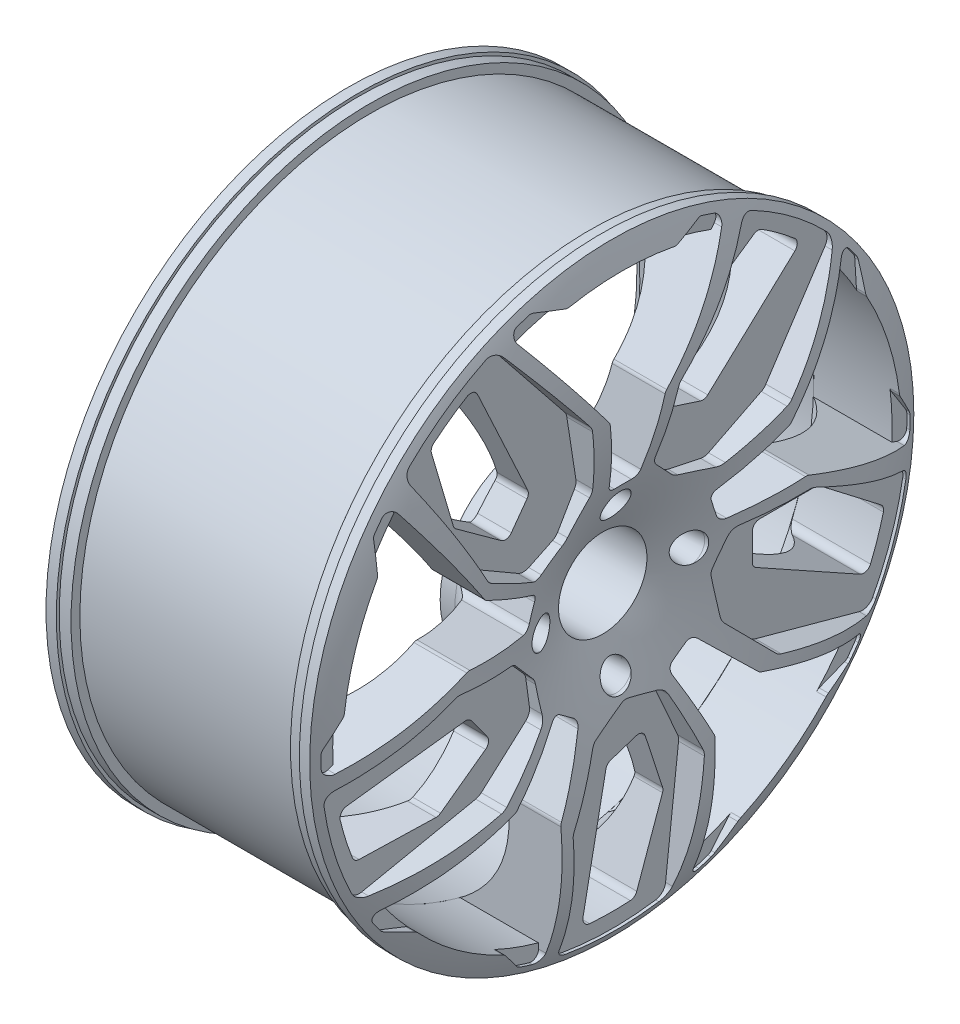
SolidWorks part; units mm, degrees
ref_plane "Płaszczyzna przednia" through (0, 0, 0) normal (0, 0, 1) x (1, 0, 0)
ref_plane "Płaszczyzna górna" through (0, 0, 0) normal (0, 1, 0) x (1, 0, 0)
ref_plane "Płaszczyzna prawa" through (0, 0, 0) normal (1, 0, 0) x (0, 0, -1)
sketch "Szkic1" plane through (0, 0, 0) normal (0, 0, 1) x (1, 0, 0)
  line L0 (-18.45, 205.2) -> (-18.45, 196.2)
  line L1 (-18.45, 196.2) -> (-26.45, 196.2)
  line L2 (-26.45, 196.2) -> (-26.45, 190.2)
  line L3 (-26.45, 190.2) -> (-189.55, 190.2)
  line L4 (-189.55, 190.2) -> (-189.55, 196.2)
  line L5 (-189.55, 196.2) -> (-197.55, 196.2)
  line L6 (-197.55, 196.2) -> (-197.55, 205.2)
  line L7 (-25.45, 205.2) -> (-25.45, 203.2)
  line L8 (-25.45, 203.2) -> (-33.45, 203.2)
  line L9 (-33.45, 203.2) -> (-33.45, 197.2)
  line L10 (-33.45, 197.2) -> (-182.55, 197.2)
  line L11 (-182.55, 197.2) -> (-182.55, 203.2)
  line L12 (-182.55, 203.2) -> (-190.55, 203.2)
  line L13 (-190.55, 203.2) -> (-190.55, 205.2)
  line L16 (75.0131, 0) -> (-270.1284, 0) construction
  line L17 (-18.45, 205.2) -> (-25.45, 205.2)
  line L18 (-190.55, 205.2) -> (-197.55, 205.2)
  line L19 (-40, 0) -> (-70, 0)
  line L20 (-70, 0) -> (-70, 65)
  line L21 (-70, 65) -> (-60, 65)
  line L22 (-108, 190.2) -> (-108, -71.7355) construction
  line L23 (-54.4873, 275.4127) -> (17.5873, 134.9873) construction
  arc A2 (-60, 65) -> (-51.3397, 70) centre (-60, 75) ccw
  spline S0 degree 2 poles (-40, 0) (26.5967, 117.4341) (-18.45, 205.2) knots 0 0 0 1 1 1
  spline S1 degree 2 poles (-51.3397, 70) (-12.7298, 148.6832) (-71.45, 190.2) knots 0 0 0 1 1 1
  dimension "D9" = 10
  dimension "D10" = 135.0532
  dimension "D11" = 30
  dimension "D14" = 5
  dimension "D1" = 9
  dimension "D2" = 8
  dimension "D3" = 6
  dimension "D5" = 165.1
  dimension "D6" = 406.4
  dimension "D7" = 40
  dimension "D8" = 65
  dimension "D12" = 10
  dimension "D13" = 45
  dimension "D15" = 25
  dimension "D17" = 38
  dimension "D4" = 7
revolve "Obrót1" add sketch "Szkic1" angle 360 about L16 region at (-32.701, 96.6315, 0)
sketch "Szkic2" plane through (0, 0, 0) normal (1, 0, 0) x (0, 0, -1)
  circle A0 centre (0, 0) radius 30.05
  dimension "D1" = 60.1
extrude "Wytnij-wyciągnięcie1" cut sketch "Szkic2" against normal through all both and the other way through all
sketch "Szkic3" plane through (0, 0, 0) normal (-1, 0, 0) x (0, 0, 1)
  line L6 (5.8045, 65) -> (-5.8045, 65)
  line L7 (-10.7285, 69.1318) -> (-18.6039, 113.7951)
  line L8 (-19.5612, 115.9707) -> (-67.0004, 177.7947)
  line L9 (10.7285, 69.1318) -> (18.6039, 113.7951)
  line L10 (19.5612, 115.9707) -> (67.0004, 177.7947)
  line L11 (18.8163, 115) -> (-18.8163, 115) construction
  line L12 (67.0004, 177.7947) -> (-67.0004, 177.7947) construction
  line L13 (-82.9434, 175.5998) -> (-29.6033, 117.2002)
  line L14 (-27.688, 113.4819) -> (-19.1975, 73.876)
  line L16 (-65.2337, 47.294) -> (-101.1668, 65.4209)
  line L17 (-104.2499, 68.1711) -> (-144.4412, 129.3521)
  line L28 (-67.0004, 177.7947) -> (-69.2362, 180.7085)
  line L29 (-55.9531, 191.2647) -> (-38.0355, 186.6557)
  line L30 (67.0004, 177.7947) -> (69.2362, 180.7085)
  line L31 (55.9531, 191.2647) -> (38.0355, 186.6557)
  line L32 (-96.1165, 160.4401) -> (-53.0369, 130.8923)
  line L33 (-51.1084, 128.3099) -> (-39.4545, 92.3363)
  line L34 (-42.6702, 86.0388) -> (-59.8062, 80.4875)
  line L35 (-64.752, 81.5825) -> (-123.9747, 136.652)
  line L36 (-59.9536, 46.6143) -> (-37.7776, 51.3684)
  line L37 (-33.6716, 53.6627) -> (-21.2368, 66.6712)
  circle A0 centre (0, 0) radius 190 construction
  arc A1 (35.8465, 186.5878) -> (-35.8465, 186.5878) centre (0, 0) ccw
  arc A3 (-58.6653, 191.2025) -> (-66.943, 188.4639) centre (0, 0) ccw
  arc A5 (67.0004, 177.7947) -> (-67.0004, 177.7947) centre (0, 0) ccw
  arc A6 (-101.6188, 160.5416) -> (-123.8286, 144.1058) centre (0, 0) ccw
  arc A7 (66.943, 188.4639) -> (58.6653, 191.2025) centre (0, 0) ccw
  arc A8 (-92.5525, 177.2965) -> (-143.4946, 139.3172) centre (0, 0) ccw
  arc A10 (-59.8062, 80.4875) -> (-64.752, 81.5825) centre (-61.3471, 85.2441) cw
  arc A11 (-123.9747, 136.652) -> (-123.8286, 144.1058) centre (-120.5699, 140.3136) cw
  arc A12 (-101.6188, 160.5416) -> (-96.1165, 160.4401) centre (-98.9447, 156.3168) cw
  arc A13 (-51.1084, 128.3099) -> (-53.0369, 130.8923) centre (-55.865, 126.769) ccw
  arc A14 (-39.4545, 92.3363) -> (-42.6702, 86.0388) centre (-44.2111, 90.7954) cw
  arc A15 (-92.5525, 177.2965) -> (-82.9434, 175.5998) centre (-88.8504, 170.2046) cw
  arc A16 (-29.6033, 117.2002) -> (-27.688, 113.4819) centre (-35.5103, 111.805) cw
  arc A17 (-19.1975, 73.876) -> (-21.2368, 66.6712) centre (-27.0197, 72.1991) cw
  arc A18 (-33.6716, 53.6627) -> (-37.7776, 51.3684) centre (-39.4545, 59.1906) cw
  arc A19 (-59.9536, 46.6143) -> (-65.2337, 47.294) centre (-61.6305, 54.4366) cw
  arc A20 (-101.1668, 65.4209) -> (-104.2499, 68.1711) centre (-97.5636, 72.5635) cw
  arc A21 (-144.4412, 129.3521) -> (-143.4946, 139.3172) centre (-137.7548, 133.7445) cw
  arc A22 (-35.8465, 186.5878) -> (-38.0355, 186.6557) centre (-36.7899, 191.4981) cw
  arc A23 (-69.2362, 180.7085) -> (-66.943, 188.4639) centre (-65.2695, 183.7523) cw
  arc A24 (-58.6653, 191.2025) -> (-55.9531, 191.2647) centre (-57.1987, 186.4224) cw
  arc A25 (35.8465, 186.5878) -> (38.0355, 186.6557) centre (36.7899, 191.4981) ccw
  arc A26 (55.9531, 191.2647) -> (58.6653, 191.2025) centre (57.1987, 186.4224) cw
  arc A27 (66.943, 188.4639) -> (69.2362, 180.7085) centre (65.2695, 183.7523) cw
  arc A28 (-19.5612, 115.9707) -> (-18.6039, 113.7951) centre (-23.5279, 112.9269) cw
  arc A29 (19.5612, 115.9707) -> (18.6039, 113.7951) centre (23.5279, 112.9269) ccw
  arc A30 (10.7285, 69.1318) -> (5.8045, 65) centre (5.8045, 70) cw
  arc A31 (-5.8045, 65) -> (-10.7285, 69.1318) centre (-5.8045, 70) cw
  point P3 (0, 65)
  point P10 (0, 115)
  point P11 (0, 177.7947)
  point P36 (-98.8084, 162.2865)
  point P43 (-87.0285, 180.0723)
  point P62 (-57.3087, 191.6135)
  point P67 (57.3087, 191.6135)
  point P70 (73.3466, 186.0652)
  point P79 (10, 65)
  point P82 (-10, 65)
  dimension "D1" = 380
  dimension "D7" = 400
  dimension "D8" = 5
  dimension "D9" = 8
  dimension "D10" = 5
  dimension "D2" = 20
  dimension "D3" = 20
  dimension "D4" = 50
  dimension "D5" = 65
  dimension "D6" = 75
extrude "Wytnij-wyciągnięcie2" cut sketch "Szkic3" along normal through all contours A1 L10 L9 L6 L7 L8 | A6 L32 L33 L34 L35 region at (0, 145.6998, 0) region at (0, 121.6456, -79.3973)
extrude "Wytnij-wyciągnięcie3" cut sketch "Szkic4<8>" along normal blind 18 contours A7 L30 A1 L31 | A3 L29 A1 L28 | A8 L13 L14 L16 L17 L32 A6 L35 L34 L33 region at (0, 185.4177, 57.6178) region at (0, 185.4177, -57.6178) region at (0, 145.167, -57.6233)
sketch "Szkic4<8>" plane through (0, 0, 0) normal (-1, 0, 0) x (0, 0, 1) same geometry as "Szkic3"
sketch "Szkic4" plane through (0, 0, 0) normal (0, 0, 1) x (1, 0, 0)
  line L0 (-70, 30.05) -> (-70, -30.05) construction
  line L1 (-70, 30.05) -> (-70, -30.05) construction
  line L2 (-70, 50) -> (-0.2742, 50)
  line L3 (-86.036, 50) -> (19.5859, 50) construction
  line L5 (-0.2742, 60) -> (-15.2742, 60)
  line L6 (-15.2742, 60) -> (-50, 56)
  line L7 (-50, 56) -> (-70, 56)
  line L8 (-70, 56) -> (-70, 50)
  line L9 (-0.2742, -129.5451) -> (-0.2742, 72.698) construction
  line L10 (-0.2742, 50) -> (-0.2742, 60)
  dimension "D1" = 6
  dimension "D2" = 10
  dimension "D3" = 50
  dimension "D4" = 15
  dimension "D5" = 20
revolve "Wycięcie-obrót1" cut sketch "Szkic4" angle 360 about L3
pattern_circular "Szyk kołowy1" count 4 every 90 about axis through (-24.5631, 0, 0) along (1, 0, 0) of "Wycięcie-obrót1" reverse direction yes
pattern_circular "Szyk kołowy2" count 5 every 72 about axis through (-24.5631, 0, 0) along (1, 0, 0) of "Wytnij-wyciągnięcie3", "Wytnij-wyciągnięcie2"
